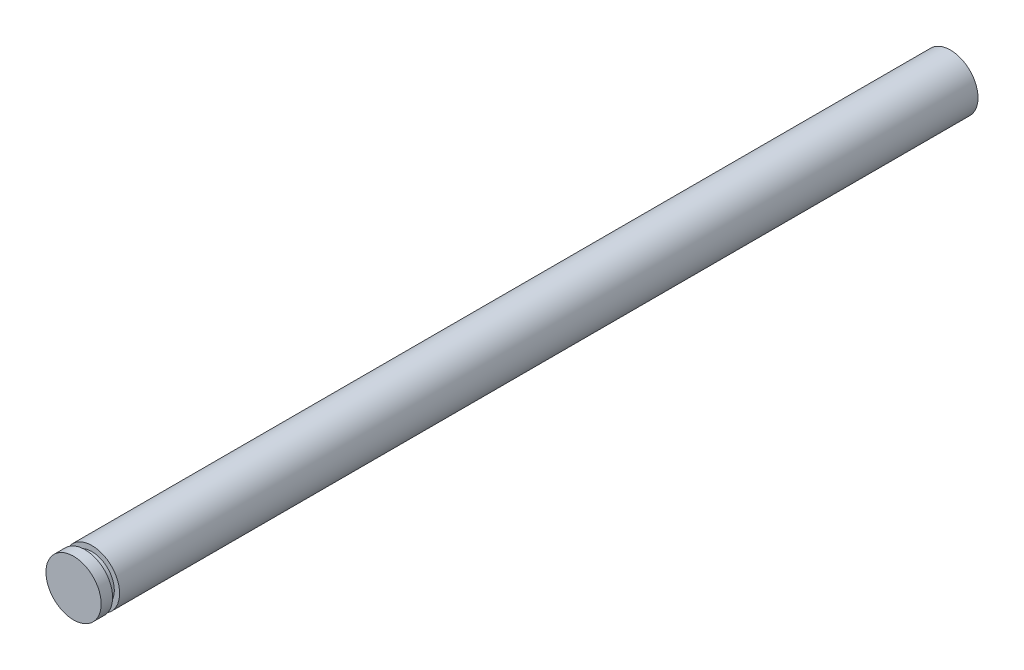
SolidWorks part; units mm, degrees
material "6061 Alloy"
ref_plane "Front Plane" through (0, 0, 0) normal (0, 0, 1) x (1, 0, 0)
ref_plane "Top Plane" through (0, 0, 0) normal (0, 1, 0) x (1, 0, 0)
ref_plane "Right Plane" through (0, 0, 0) normal (1, 0, 0) x (0, 0, -1)
sketch "Sketch1" plane through (0, 0, 0) normal (0, 0, 1) x (1, 0, 0)
  circle A0 centre (0, 0) radius 2
  dimension "D1" = 4
extrude "Boss-Extrude1" add sketch "Sketch1" along normal mid plane 63.5
sketch "Sketch2" plane through (0, 0, 0) normal (1, 0, 0) x (0, 0, -1)
  line L0 (31.75, 2) -> (-31.75, 2) construction
  line L1 (-30.4165, 2) -> (-30.9245, 2)
  line L2 (-30.4165, 2) -> (-30.4165, 1.619)
  line L3 (-30.4165, 1.619) -> (-30.9245, 1.619)
  line L4 (-30.9245, 2) -> (-30.9245, 1.619)
  line L5 (-30.1625, 19.05) -> (-30.1625, 0) construction
  dimension "D1" = 0.254
  dimension "D2" = 0.508
  dimension "D3" = 0.381
ref_axis "Axis1" through (0, 0, 31.75) along (0, 0, -1)
revolve "Cut-Revolve1" cut sketch "Sketch2" angle 360 about axis through (0, 0, 31.75) along (0, 0, -1)
